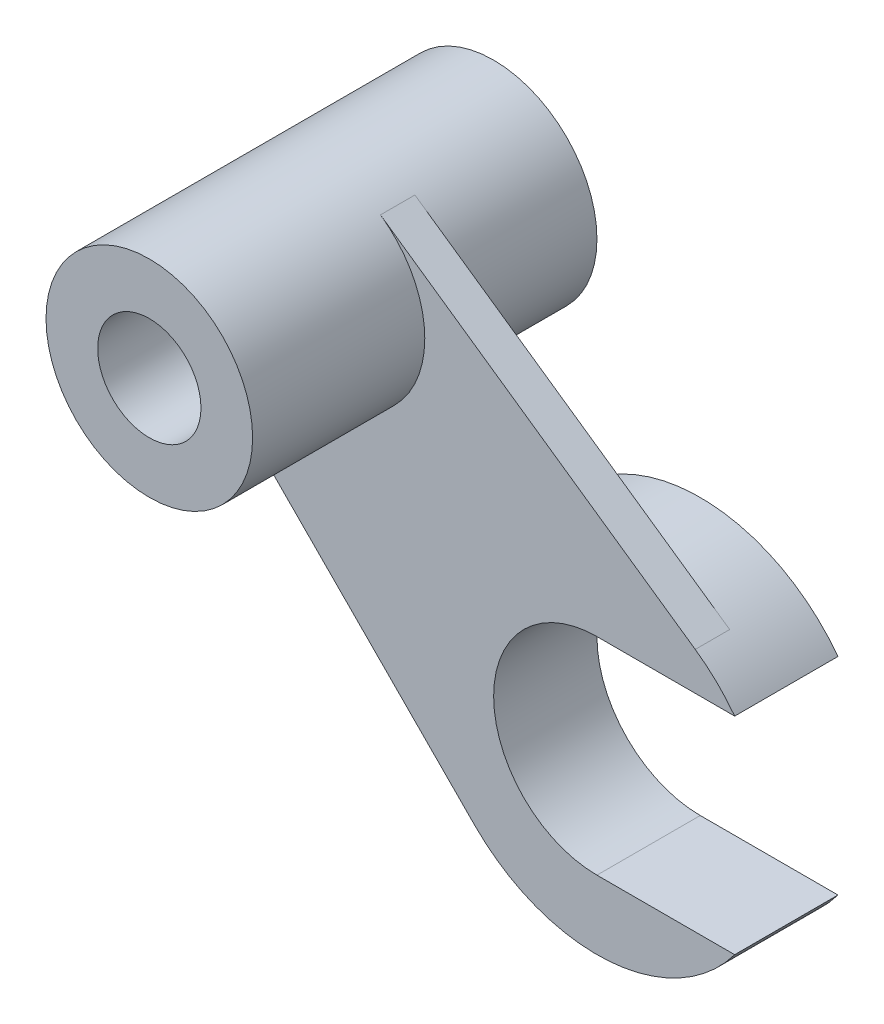
SolidWorks part; units mm, degrees
ref_plane "Front Plane" through (0, 0, 0) normal (0, 0, 1) x (1, 0, 0)
ref_plane "Top Plane" through (0, 0, 0) normal (0, 1, 0) x (1, 0, 0)
ref_plane "Right Plane" through (0, 0, 0) normal (1, 0, 0) x (0, 0, -1)
sketch "Sketch1" plane through (0, 0, 0) normal (0, 0, 1) x (1, 0, 0)
  circle A0 centre (0, 0) radius 30
  dimension "D1" = 60
extrude "Boss-Extrude1" add sketch "Sketch1" against normal blind 50 and the other way blind 50
sketch "Sketch3" plane through (0, 0, 0) normal (0, 0, 1) x (1, 0, 0)
  circle A1 centre (80, -80) radius 50
  dimension "D1" = 80
  dimension "D3" = 100
  dimension "D2" = 80
extrude "Boss-Extrude2" add sketch "Sketch3" against normal blind 30 separate body
sketch "Sketch4" plane through (0, 0, 0) normal (0, 0, 1) x (1, 0, 0)
  line L0 (17.1291, 24.6291) -> (108.5485, -38.9515)
  line L3 (-30, -40) -> (-30, 0)
  line L5 (-30, -40) -> (44.4774, -115.1872)
  line L6 (-30, 0) -> (17.1291, 24.6291)
  line L7 (44.4774, -115.1872) -> (108.5485, -38.9515)
  circle A0 centre (0, 0) radius 30 construction
  circle A1 centre (80, -80) radius 50 construction
  dimension "D1" = 40
  dimension "D2" = 30
extrude "Boss-Extrude3" add sketch "Sketch4" against normal blind 10 contours L3 L6 L0 L7 L5
hole_wizard "Ø2.0mm Dowel Hole1" positions "Sketch5" profile "Sketch6" hole size "Ø2.0" standard "ISO"
sketch "Sketch5" plane through (0, 0, 50) normal (0, 0, 1) x (1, 0, 0)
  point P0 (0, 0)
sketch "Sketch6" plane through (0, 0, 50) normal (1, 0, 0) x (0, -1, 0)
  line L0 (0, 0) -> (0, 100)
  line L1 (0, 100) -> (15, 100)
  line L2 (15, 100) -> (15, 0)
  line L5 (15, 0) -> (0, 0)
  line L10 (0, 100) -> (-15, 100) construction
  line L11 (0, -6.35) -> (0, 107.95) construction
  dimension "Hole Dia." = 30
  dimension "Hole Depth" = 100
  dimension "Drill Angle" = 180
hole_wizard "Ø2.0mm Dowel Hole2" positions "Sketch9" profile "Sketch10" hole size "Ø2.0" standard "ISO"
sketch "Sketch9" plane through (0, 0, 0) normal (0, 0, 1) x (1, 0, 0)
  point P0 (80, -80)
  dimension "D1" = 80
  dimension "D2" = 80
sketch "Sketch10" plane through (80, -80, 0) normal (1, 0, 0) x (0, -1, 0)
  line L0 (0, 0) -> (0, 100)
  line L1 (0, 100) -> (30, 100)
  line L2 (30, 100) -> (30, 0)
  line L5 (30, 0) -> (0, 0)
  line L10 (0, 100) -> (-30, 100) construction
  line L11 (0, -6.35) -> (0, 107.95) construction
  dimension "Hole Dia." = 60
  dimension "Hole Depth" = 100
  dimension "Drill Angle" = 180
sketch "Sketch11" plane through (0, 0, -30) normal (0, 0, -1) x (-1, 0, 0)
  line L5 (-80, -110) -> (-130.7186, -110)
  line L6 (-80, -110) -> (-80, -50)
  line L7 (-80, -50) -> (-130.7186, -50)
  line L8 (-130.7186, -110) -> (-130.7186, -50)
  circle A1 centre (-80, -80) radius 30 construction
extrude "Cut-Extrude1" cut sketch "Sketch11" against normal blind 40
